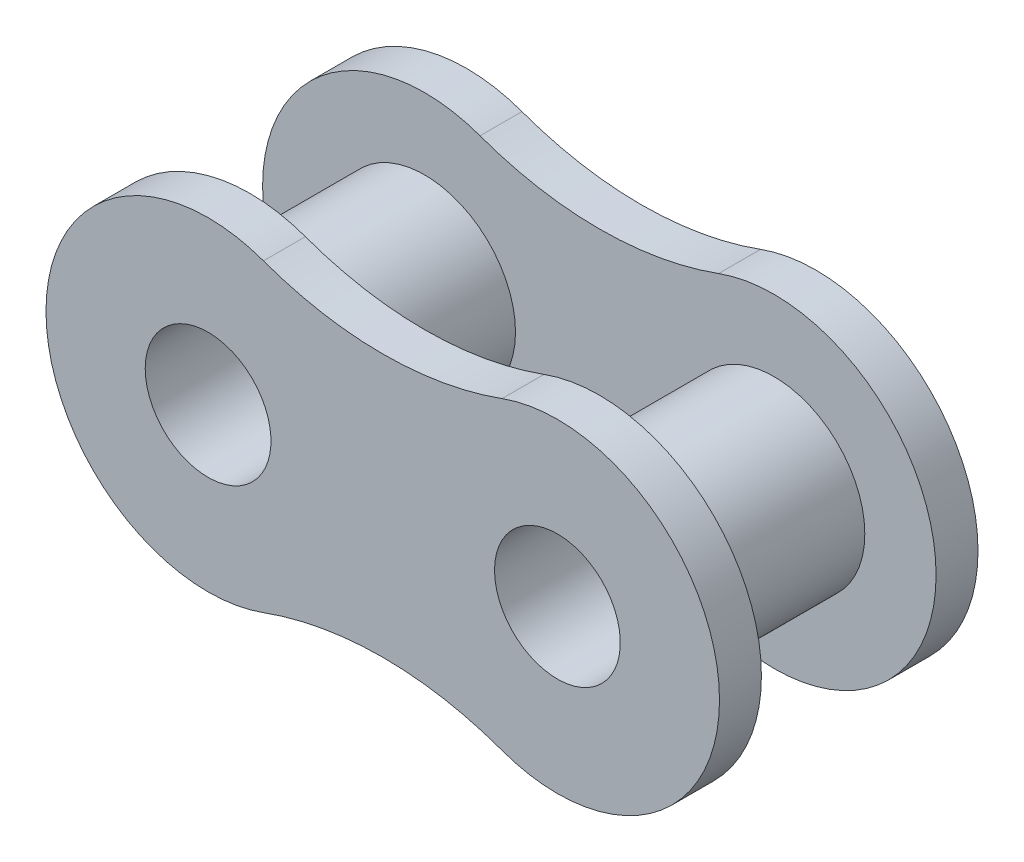
SolidWorks part; units mm, degrees
material "Rubber"
ref_plane "Front" through (0, 0, 0) normal (0, 0, 1) x (1, 0, 0)
ref_plane "Top" through (0, 0, 0) normal (0, 1, 0) x (1, 0, 0)
ref_plane "Right" through (0, 0, 0) normal (1, 0, 0) x (0, 0, -1)
sketch "Sketch1" plane through (0, 0, 0) normal (0, 0, 1) x (1, 0, 0)
  arc A0 (-1.0063, -2.7692) -> (-1.0063, 2.7692) centre (0, 0) ccw
  arc A1 (-5.3437, 2.7692) -> (-5.3437, -2.7692) centre (-6.35, 0) ccw
  circle A2 centre (0, 0) radius 1.143
  circle A3 centre (-6.35, 0) radius 1.143
  arc A4 (-1.0063, -2.7692) -> (-5.3437, -2.7692) centre (-3.175, -8.7374) ccw
  arc A5 (-5.3437, 2.7692) -> (-1.0063, 2.7692) centre (-3.175, 8.7374) ccw
  dimension "D2" = 5.8928
  dimension "D3" = 2.286
  dimension "D4" = 12.7
  dimension "D1" = 6.35
extrude "inner link s1" add sketch "Sketch1" along normal blind 0.762 from offset 1.5875
mirror "inner link s2" about plane through (0, 0, 0) normal (0, 0, 1) of bodies 101
sketch "Sketch3" plane through (0, 0, 1.5875) normal (0, 0, -1) x (-1, 0, 0)
  circle A0 centre (0, 0) radius 1.143
  circle A1 centre (0, 0) radius 1.143 construction
  circle A2 centre (6.35, 0) radius 1.143
  circle A3 centre (6.35, 0) radius 1.143 construction
  circle A4 centre (0, 0) radius 1.651
  circle A5 centre (6.35, 0) radius 1.651
  dimension "D1" = 3.302
extrude "tubes" add sketch "Sketch3" along normal up to surface (3.175 mm away) up to face at (1.143, 0, -1.5875)
